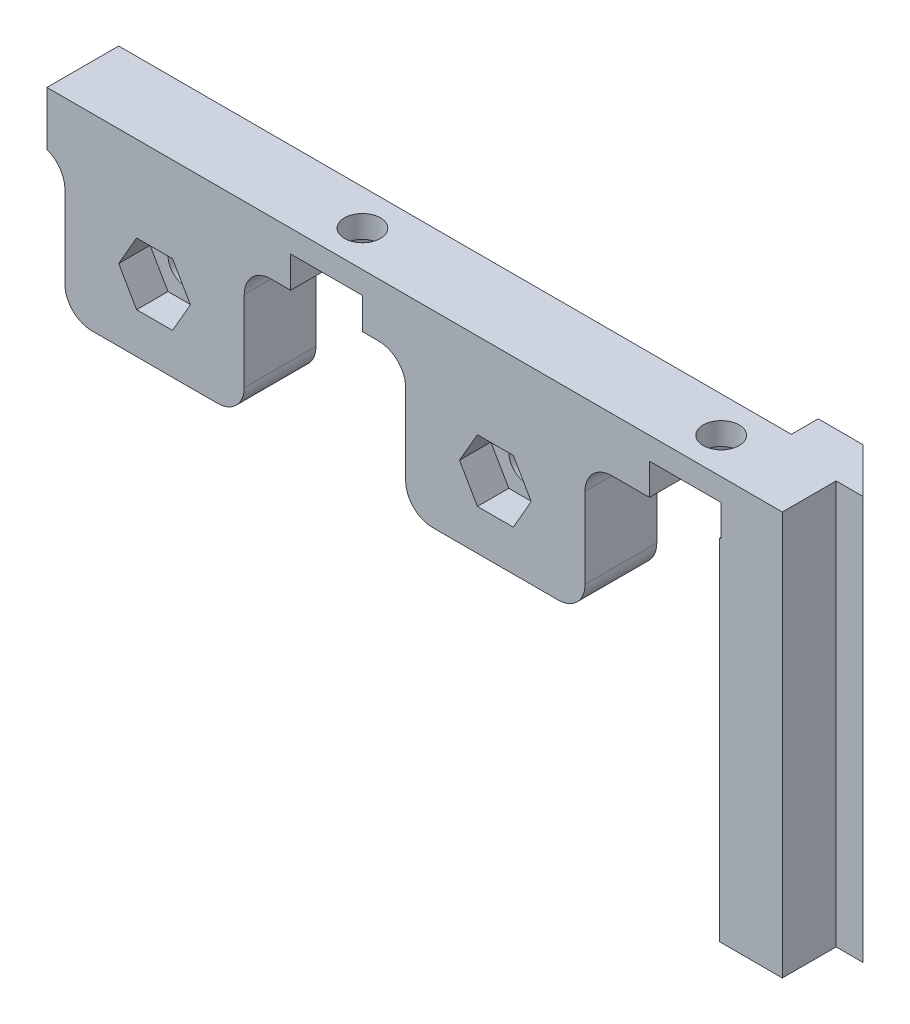
SolidWorks part; units mm, degrees
ref_plane "Plan de face" through (0, 0, 0) normal (0, 0, 1) x (1, 0, 0)
ref_plane "Plan de dessus" through (0, 0, 0) normal (0, 1, 0) x (1, 0, 0)
ref_plane "Plan de droite" through (0, 0, 0) normal (1, 0, 0) x (0, 0, -1)
sketch "Esquisse1" plane through (0, 0, 0) normal (0, 1, 0) x (1, 0, 0)
  line L0 (77.5, -2.5) -> (72.5, 2.5)
  line L1 (72.5, 2.5) -> (67.5, 2.5)
  line L2 (67.5, 2.5) -> (67.5, -0.5)
  line L3 (67.5, -0.5) -> (-7.5, -0.5)
  line L4 (-7.5, -0.5) -> (-7.5, -8.5)
  line L5 (74.5, -2.5) -> (77.5, -2.5)
  line L6 (74.5, -2.5) -> (74.5, -8.5)
  line L7 (74.5, -8.5) -> (-7.5, -8.5)
  circle A0 centre (63.6795, -4.5) radius 2
  circle A1 centre (23.6795, -4.5) radius 2
  dimension "D1" = 5
  dimension "D2" = 135
  dimension "D3" = 3
  dimension "D4" = 8
  dimension "D5" = 75
  dimension "D6" = 3
extrude "Boss.-Extru.1" add sketch "Esquisse1" along normal blind 45
sketch "Esquisse2" plane through (0, 0, 0.5) normal (0, 0, -1) x (-1, 0, 0)
  line L0 (-67.5, 45) -> (-67.5, 0) construction
  line L1 (7.5, 0) -> (-67.5, 0)
  line L2 (7.5, 0) -> (7.5, 39)
  line L3 (7.5, 39) -> (-67.5, 39)
  line L4 (-67.5, 0) -> (-67.5, 39)
  line L5 (7.5, 0) -> (-67.5, 39) construction
  line L6 (7.5, 39) -> (-67.5, 0) construction
  line L7 (-67.5, 45) -> (7.5, 45) construction
  point P4 (-30, 19.5)
  dimension "D1" = 6
extrude "Enlèv. mat.-Extru.1" cut sketch "Esquisse2" against normal blind 45
sketch "Esquisse3" plane through (0, 39, 0) normal (0, -1, 0) x (1, 0, 0)
  line L0 (65.6795, 1.0359) -> (61.6795, 1.0359)
  line L1 (61.6795, 1.0359) -> (59.6795, 4.5)
  line L2 (65.6795, 7.9641) -> (67.6795, 4.5) construction
  line L3 (61.6795, 7.9641) -> (65.6795, 7.9641) construction
  line L4 (61.6795, 7.9641) -> (59.6795, 4.5) construction
  line L5 (67.6795, 4.5) -> (65.6795, 1.0359)
  line L6 (65.6795, 1.0359) -> (61.6795, 7.9641) construction
  line L7 (61.6795, 1.0359) -> (65.6795, 7.9641) construction
  line L8 (67.6795, 4.5) -> (67.6795, 8.5)
  line L9 (59.6795, 4.5) -> (59.6795, 8.5)
  line L10 (59.6795, 8.5) -> (67.6795, 8.5)
  line L11 (25.6795, 1.0359) -> (21.6795, 1.0359)
  line L12 (21.6795, 1.0359) -> (19.6795, 4.5)
  line L13 (25.6795, 7.9641) -> (27.6795, 4.5) construction
  line L14 (21.6795, 7.9641) -> (25.6795, 7.9641) construction
  line L15 (21.6795, 7.9641) -> (19.6795, 4.5) construction
  line L16 (27.6795, 4.5) -> (25.6795, 1.0359)
  line L17 (25.6795, 1.0359) -> (21.6795, 7.9641) construction
  line L18 (21.6795, 1.0359) -> (25.6795, 7.9641) construction
  line L19 (27.6795, 4.5) -> (27.6795, 8.5)
  line L20 (19.6795, 4.5) -> (19.6795, 8.5)
  line L21 (19.6795, 8.5) -> (27.6795, 8.5)
  line L22 (-7.5, 8.5) -> (67.5, 8.5) construction
  circle A0 centre (63.6795, 4.5) radius 3.4641 construction
  circle A1 centre (23.6795, 4.5) radius 3.4641 construction
  point P10 (48.6795, 4.5)
  point P22 (8.6795, 4.5)
  dimension "D1" = 4
  dimension "D2" = 4
extrude "Enlèv. mat.-Extru.2" cut sketch "Esquisse3" against normal blind 3.5
sketch "Esquisse4" plane through (0, 39, 0) normal (0, -1, 0) x (1, 0, 0)
  line L0 (27.6795, 8.5) -> (59.6795, 8.5) construction
  line L1 (52.5, 8.5) -> (32.5, 8.5)
  line L2 (52.5, 8.5) -> (52.5, 0.5)
  line L3 (52.5, 0.5) -> (32.5, 0.5)
  line L4 (32.5, 8.5) -> (32.5, 0.5)
  line L5 (52.5, 8.5) -> (32.5, 0.5) construction
  line L6 (52.5, 0.5) -> (32.5, 8.5) construction
  line L7 (-7.5, 0.5) -> (67.5, 0.5) construction
  line L8 (-7.5, 8.5) -> (19.6795, 8.5) construction
  line L9 (14.5, 8.5) -> (-5.5, 8.5)
  line L10 (14.5, 8.5) -> (14.5, 0.5)
  line L11 (14.5, 0.5) -> (-5.5, 0.5)
  line L12 (-5.5, 8.5) -> (-5.5, 0.5)
  line L13 (14.5, 8.5) -> (-5.5, 0.5) construction
  line L14 (14.5, 0.5) -> (-5.5, 8.5) construction
  line L15 (-7.5, 8.5) -> (-7.5, 0.5) construction
  point P4 (42.5, 4.5)
  point P13 (4.5, 4.5)
  dimension "D1" = 20
  dimension "D2" = 20
  dimension "D3" = 2
  dimension "D4" = 40
extrude "Boss.-Extru.2" add sketch "Esquisse4" along normal blind 15
fillet "Congé1" radius 3 8 edges at (14.5, 39, 4.5) (-5.5, 39, 4.5) (32.5, 39, 4.5) (52.5, 39, 4.5) (-5.5, 24, 4.5) (32.5, 24, 4.5) (52.5, 24, 4.5) (14.5, 24, 4.5)
sketch "Esquisse5" plane through (0, 0, 8.5) normal (0, 0, 1) x (1, 0, 0)
  line L0 (4.5, 24) -> (4.5, 49.1049) construction
  line L1 (42.5, 24) -> (42.5, 54.774) construction
  line L2 (-8.4875, 32) -> (66.7076, 32) construction
  line L3 (6.5, 28.5359) -> (2.5, 28.5359)
  line L4 (2.5, 28.5359) -> (0.5, 32)
  line L5 (6.5, 35.4641) -> (8.5, 32)
  line L6 (2.5, 35.4641) -> (6.5, 35.4641)
  line L7 (2.5, 35.4641) -> (0.5, 32)
  line L8 (8.5, 32) -> (6.5, 28.5359)
  line L9 (6.5, 28.5359) -> (2.5, 35.4641) construction
  line L10 (2.5, 28.5359) -> (6.5, 35.4641) construction
  line L11 (8.5, 32) -> (9.7486, 32)
  line L12 (44.5, 28.5359) -> (40.5, 28.5359)
  line L13 (40.5, 28.5359) -> (38.5, 32)
  line L14 (44.5, 35.4641) -> (46.5, 32)
  line L15 (40.5, 35.4641) -> (44.5, 35.4641)
  line L16 (40.5, 35.4641) -> (38.5, 32)
  line L17 (46.5, 32) -> (44.5, 28.5359)
  line L18 (44.5, 28.5359) -> (40.5, 35.4641) construction
  line L19 (40.5, 28.5359) -> (44.5, 35.4641) construction
  line L20 (46.5, 32) -> (47.7486, 32)
  line L22 (11.5, 24) -> (-2.5, 24) construction
  line L23 (49.5, 24) -> (35.5, 24) construction
  circle A0 centre (4.5, 32) radius 3.4641 construction
  circle A1 centre (42.5, 32) radius 3.4641 construction
  point P6 (4.5, 32)
  point P7 (42.5, 32)
  point P17 (42.5, 32)
  point P29 (4.9668, 49.1049)
  point P30 (4.5, 24)
  point P31 (42.5, 24)
  dimension "D1" = 4
  dimension "D2" = 4
  dimension "D3" = 8
extrude "Enlèv. mat.-Extru.3" cut sketch "Esquisse5" against normal blind 3.5 contours L8 L5 L6 L7 L4 L3 | L17 L14 L15 L16 L13 L12 region at (4.5, 32, 8.5) region at (42.5, 32, 8.5)
sketch "Esquisse7" plane through (0, 0, 5) normal (0, 0, 1) x (1, 0, 0)
  line L0 (2.5, 35.4641) -> (6.5, 28.5359) construction
  line L1 (6.5, 35.4641) -> (2.5, 28.5359) construction
  line L2 (40.5, 35.4641) -> (44.5, 28.5359) construction
  line L3 (44.5, 35.4641) -> (40.5, 28.5359) construction
  line L4 (40.5, 28.5359) -> (38.5, 32) construction
  line L5 (40.5, 28.5359) -> (38.5, 32) construction
  circle A0 centre (4.5, 32) radius 2
  circle A1 centre (42.5, 32) radius 2
  point P11 (4.5, 32)
  point P12 (40.5, 35.4641)
  point P18 (44.5, 28.5359)
  point P20 (40.5, 28.5359)
  point P25 (44.5, 35.4641)
  point P27 (42.5, 32)
  dimension "D1" = 4
extrude "Enlèv. mat.-Extru.4" cut sketch "Esquisse7" against normal through all both and the other way through all
